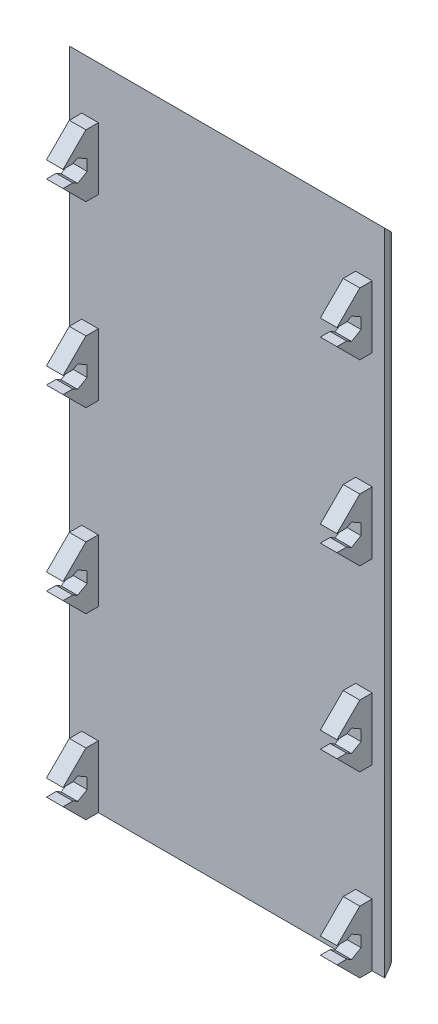
SolidWorks part; units mm, degrees
ref_plane "Front Plane" through (0, 0, 0) normal (0, 0, 1) x (1, 0, 0)
ref_plane "Top Plane" through (0, 0, 0) normal (0, 1, 0) x (1, 0, 0)
ref_plane "Right Plane" through (0, 0, 0) normal (1, 0, 0) x (0, 0, -1)
sketch "Sketch1" plane through (0, 0, 0) normal (0, 1, 0) x (1, 0, 0)
  line L0 (-9.2151, 0) -> (-9.2151, -10)
  line L1 (-9.2151, -10) -> (-5.2151, -10)
  line L2 (-5.2151, -10) -> (-5.2151, 0)
  line L3 (-5.2151, 0) -> (56.7849, 0)
  line L4 (56.7849, 0) -> (56.7849, -10)
  line L5 (56.7849, -10) -> (60.7849, -10)
  line L6 (60.7849, -10) -> (60.7849, 0)
  line L7 (60.7849, 0) -> (63.7849, 0)
  line L8 (-9.2151, 0) -> (-12.2151, 0)
  line L9 (-12.2151, 0) -> (-8.1737, 7)
  line L10 (-8.1737, 7) -> (59.7434, 7)
  line L11 (59.7434, 7) -> (63.7849, 0)
  line L12 (25.7849, 7) -> (25.7849, 0) construction
  dimension "D1" = 3
  dimension "D2" = 10
  dimension "D3" = 70
  dimension "D4" = 7
  dimension "D5" = 4
  dimension "D6" = 60
extrude "Boss-Extrude1" add sketch "Sketch1" along normal blind 156.5
sketch "Sketch4" plane through (60.7849, 0, 0) normal (1, 0, 0) x (0, 0, -1)
  line L0 (0, 156.5) -> (0, 0) construction
  line L1 (-37.5185, 156.5) -> (0, 156.5)
  line L2 (-37.5185, 156.5) -> (-37.5185, 144)
  line L3 (-37.5185, 144) -> (0, 144)
  line L4 (0, 156.5) -> (0, 144)
  line L5 (-37.5185, 156.5) -> (0, 144) construction
  line L6 (-37.5185, 144) -> (0, 156.5) construction
  line L7 (-10, 156.5) -> (0, 156.5) construction
  point P0 (-18.7592, 150.25)
  dimension "D1" = 12.5
extrude "Cut-Extrude1" cut sketch "Sketch4" against normal through all
sketch "Sketch5" plane through (60.7849, 0, 0) normal (1, 0, 0) x (0, 0, -1)
  line L0 (0, 156.5) -> (0, 0) construction
  line L1 (-33.3149, 129) -> (0, 129)
  line L2 (-33.3149, 129) -> (-33.3149, 101)
  line L3 (-33.3149, 101) -> (0, 101)
  line L4 (0, 129) -> (0, 101)
  line L5 (-33.3149, 129) -> (0, 101) construction
  line L6 (-33.3149, 101) -> (0, 129) construction
  line L7 (-10, 144) -> (0, 144) construction
  point P0 (-16.6574, 115)
  dimension "D1" = 28
  dimension "D2" = 15
extrude "Cut-Extrude2" cut sketch "Sketch5" against normal through all
sketch "Sketch6" plane through (0, 0, 0) normal (1, 0, 0) x (0, 0, -1)
  line L0 (-10, 144) -> (-10, 129) construction
  line L1 (-2.7, 137.8279) -> (-5, 139.1558)
  line L2 (-5, 139.1558) -> (-7.3, 137.8279)
  line L3 (-7.3, 137.8279) -> (-7.3, 135.1721)
  line L4 (-7.3, 135.1721) -> (-5, 133.8442)
  line L5 (-5, 133.8442) -> (-2.7, 135.1721)
  line L6 (-2.7, 135.1721) -> (-2.7, 137.8279)
  line L7 (-10, 144) -> (0, 144) construction
  line L8 (-6.15, 138.4919) -> (-10, 138.4919)
  line L9 (-6.15, 134.5081) -> (-10, 134.5081)
  line L10 (-10, 134.5081) -> (-10, 138.4919)
  circle A1 centre (-5, 136.5) radius 2.3 construction
  dimension "D1" = 4.6
  dimension "D2" = 7.5
  dimension "D3" = 5
extrude "Cut-Extrude3" cut sketch "Sketch6" against normal through all and the other way through all contours L10 L9 L4 L3 L2 L8 | L5 L6 L1 L2 L3 L4 region at (0, 136.5, 5) region at (0, 136.5, 8.5351)
pattern_linear "LPattern1" count 4 spacing 43 along (0, -1, 0) of "Cut-Extrude2", "Cut-Extrude3"
chamfer "Chamfer3" distance 7 angle 45 1 edges at (25.7849, 156.5, -7)
fillet "Fillet1" radius 8 2 edges at (-8.1737, 74.75, -7) (59.7434, 74.75, -7)
chamfer "Chamfer5" distance 7 angle 45 16 edges at (58.7849, 43, 10) (58.7849, 144, 10) (58.7849, 129, 10) (-7.2151, 144, 10) (-7.2151, 129, 10) (-7.2151, 101, 10) (-7.2151, 86, 10) (58.7849, 101, 10) (58.7849, 86, 10) (58.7849, 58, 10) (58.7849, 0, 10) (58.7849, 15, 10) (-7.2151, 0, 10) (-7.2151, 15, 10) (-7.2151, 58, 10) (-7.2151, 43, 10)
sketch "Sketch7" plane through (0, 0, -7) normal (0, 0, -1) x (-1, 0, 0)
  line L8 (3.5549, 82.737) -> (-11.316, 82.737) construction
  line L14 (-11.316, 128.6101) -> (-40.2538, 128.6101) construction
  line L20 (-11.316, 128.6101) -> (-11.316, 82.737) construction
  line L22 (-40.2538, 128.6101) -> (-40.2538, 82.737) construction
  line L23 (-11.316, 82.737) -> (-40.2538, 82.737) construction
  line L24 (3.5549, 0) -> (3.5549, 149.5) construction
  line L25 (-11.316, 127.6101) -> (-11.316, 116.1874)
  line L26 (-12.316, 128.6101) -> (-39.2538, 128.6101)
  line L27 (-11.316, 115.6101) -> (-40.2538, 115.6101) construction
  line L28 (-40.2538, 127.6101) -> (-40.2538, 115.6101)
  line L29 (-40.2538, 82.737) -> (-55.1246, 82.737) construction
  line L30 (-55.1246, 149.5) -> (-55.1246, 0) construction
  line L31 (-11.316, 149.5) -> (-11.316, 128.6101) construction
  line L32 (3.5549, 149.5) -> (-55.1246, 149.5) construction
  line L35 (-11.316, 107.5272) -> (-17.816, 103.7744)
  line L38 (-25.316, 99.4443) -> (-39.7538, 91.1086)
  line L39 (-11.316, 107.5272) -> (-11.316, 93.237)
  line L40 (-40.2538, 90.2426) -> (-40.2538, 82.737)
  line L41 (-40.2538, 82.737) -> (-32.316, 87.3199)
  line L42 (-32.316, 87.3199) -> (-32.316, 93.237) construction
  line L43 (-18.316, 102.9084) -> (-18.316, 93.237)
  line L44 (-11.316, 93.237) -> (-32.316, 93.237) construction
  line L45 (-25.316, 99.4443) -> (-25.316, 93.237)
  line L46 (-18.316, 93.237) -> (-25.316, 93.237) construction
  line L47 (-39.7538, 107.2744) -> (-18.566, 119.5072)
  line L48 (-40.2538, 115.6101) -> (-40.2538, 106.9857) construction
  line L49 (-11.316, 82.737) -> (-40.2538, 82.737) construction
  line L50 (-40.2538, 106.4084) -> (-40.2538, 100.5631)
  line L51 (-32.316, 87.3199) -> (-30.9714, 88.0962)
  line L52 (-11.816, 115.3214) -> (-31.566, 103.9187)
  line L53 (-33.2538, 121.1101) -> (-33.2538, 119.3988)
  line L54 (-31.566, 103.0527) -> (-25.316, 99.4443)
  line L55 (-32.316, 95.4028) -> (-39.7538, 99.6971)
  line L56 (-33.5038, 118.9657) -> (-40.2538, 115.0686)
  line L57 (-40.2538, 115.0686) -> (-40.2538, 115.6101)
  line L58 (-32.7538, 121.6101) -> (-18.816, 121.6101)
  line L59 (-18.316, 121.1101) -> (-18.316, 119.9402)
  line L60 (-11.316, 121.6101) -> (-18.316, 121.6101) construction
  line L61 (-33.2538, 121.6101) -> (-40.2538, 121.6101) construction
  line L62 (-40.2538, 128.6101) -> (-11.316, 128.6101) construction
  line L63 (-11.316, 128.6101) -> (-11.316, 82.737) construction
  arc A7 (-11.316, 93.237) -> (-32.316, 93.237) centre (-21.816, 93.237) cw
  arc A8 (-18.316, 93.237) -> (-25.316, 93.237) centre (-21.816, 93.237) cw
  arc A9 (-17.816, 103.7744) -> (-18.316, 102.9084) centre (-17.316, 102.9084) ccw
  arc A10 (-11.816, 115.3214) -> (-11.316, 116.1874) centre (-12.316, 116.1874) ccw
  arc A11 (-11.316, 127.6101) -> (-12.316, 128.6101) centre (-12.316, 127.6101) ccw
  arc A12 (-39.7538, 91.1086) -> (-40.2538, 90.2426) centre (-39.2538, 90.2426) ccw
  arc A13 (-39.2538, 128.6101) -> (-40.2538, 127.6101) centre (-39.2538, 127.6101) ccw
  arc A14 (-40.2538, 106.4084) -> (-39.7538, 107.2744) centre (-39.2538, 106.4084) cw
  arc A15 (-39.7538, 99.6971) -> (-40.2538, 100.5631) centre (-39.2538, 100.5631) cw
  arc A16 (-32.7538, 121.6101) -> (-33.2538, 121.1101) centre (-32.7538, 121.1101) ccw
  arc A17 (-33.5038, 118.9657) -> (-33.2538, 119.3988) centre (-33.7538, 119.3988) ccw
  arc A18 (-18.316, 121.1101) -> (-18.816, 121.6101) centre (-18.816, 121.1101) ccw
  arc A19 (-18.566, 119.5072) -> (-18.316, 119.9402) centre (-18.816, 119.9402) ccw
  arc A20 (-31.566, 103.0527) -> (-31.566, 103.9187) centre (-31.316, 103.4857) cw
  point P59 (-40.2538, 106.9857)
  point P63 (-40.2538, 99.9857)
  dimension "D11" = 7
  dimension "D12" = 30
  dimension "D10" = 7
  dimension "D14" = 0.5
  dimension "D16" = 7
  dimension "D6" = 7
  dimension "D13" = 1
  dimension "D2" = 1
  dimension "0.5" = 1
  dimension "D18" = 1
  dimension "D4" = 0.5
  dimension "D1" = 7
  dimension "D3" = 7
  dimension "D5" = 7
  dimension "D7" = 7
  dimension "D8" = 7
  dimension "D9" = 7
  dimension "D15" = 30
  dimension "D17" = 7
extrude "Cut-Extrude4" cut sketch "Sketch7" against normal blind 1 contours L54 A20 L52 A10 L25 A11 L26 A13 L28 L57 L56 L53 L58 L59 L47 A14 L50 A15 L55 L38 | L38 A12 L40 L41 L51 A7 L39 L35 A9 L43 A8 L45 region at (11.7564, 121.8988, -7) region at (25.697, 96.3406, -7)
sketch "Sketch8" plane through (0, 0, -7) normal (0, 0, -1) x (-1, 0, 0)
  line L0 (-40.2538, 128.6101) -> (-40.2538, 43.6101) construction
  line L1 (-55.1246, 149.5) -> (-55.1246, 0) construction
  line L2 (-25.7849, 128.6101) -> (-55.1246, 128.6101) construction
  line L3 (-12.316, 128.6101) -> (-39.2538, 128.6101) construction
  line L5 (-40.2538, 127.6101) -> (-40.2538, 115.0686) construction
  text T0 "DREAm" font "VALORANT" height in points 24
  dimension "D1" = 85
extrude "Cut-Extrude5" cut sketch "Sketch8" against normal blind 1
fillet "Fillet2" radius 0.5 2 edges at (32.316, 95.4028, -6.5) (25.316, 99.4443, -6.5)
sketch "Sketch9" plane through (0, 0, -7) normal (0, 0, -1) x (-1, 0, 0)
  line L0 (-13.816, 71.5072) -> (-25.316, 71.5072)
  line L1 (-25.316, 71.5072) -> (-25.316, 69.0072)
  line L2 (-25.316, 69.0072) -> (-13.816, 69.0072)
  line L3 (-13.816, 69.0072) -> (-13.816, 64.7572)
  line L4 (-13.816, 64.7572) -> (-11.316, 64.7572)
  line L5 (-11.316, 64.7572) -> (-11.316, 75.7572)
  line L6 (-11.316, 75.7572) -> (-13.816, 75.7572)
  line L7 (-13.816, 75.7572) -> (-13.816, 71.5072)
  line L8 (-11.316, 62.2572) -> (-11.316, 59.7572)
  line L9 (-11.316, 59.7572) -> (-25.316, 59.7572)
  line L10 (-25.316, 59.7572) -> (-25.316, 62.2572)
  line L11 (-25.316, 62.2572) -> (-11.316, 62.2572)
  line L12 (-11.316, 75.7572) -> (-11.316, 12.6828) construction
  line L13 (-25.316, 71.5072) -> (-25.316, 10.6582) construction
  line L14 (-11.316, 57.2572) -> (-25.316, 57.2572)
  line L15 (-25.316, 57.2572) -> (-25.316, 54.7572)
  line L16 (-25.316, 54.7572) -> (-16.316, 54.7572)
  line L17 (-16.316, 54.7572) -> (-25.316, 49.5611)
  line L18 (-25.316, 49.5611) -> (-25.316, 47.0611)
  line L19 (-25.316, 47.0611) -> (-16.316, 47.0611)
  line L20 (-16.316, 47.0611) -> (-25.316, 41.8649)
  line L21 (-25.316, 41.8649) -> (-25.316, 41.4782)
  line L22 (-25.316, 41.4782) -> (-20.9858, 41.4782)
  line L23 (-20.9858, 41.4782) -> (-11.316, 47.0611)
  line L24 (-11.316, 47.0611) -> (-11.316, 49.5611)
  line L25 (-11.316, 49.5611) -> (-20.316, 49.5611)
  line L26 (-20.316, 49.5611) -> (-11.316, 54.7572)
  line L27 (-11.316, 54.7572) -> (-11.316, 57.2572)
  line L28 (-11.316, 47.0611) -> (-25.316, 38.9782) construction
  line L29 (-25.316, 38.9782) -> (-11.316, 38.9782)
  line L30 (-11.316, 38.9782) -> (-11.316, 36.4782)
  line L31 (-11.316, 36.4782) -> (-25.316, 28.3953)
  line L32 (-25.316, 28.3953) -> (-25.316, 31.282)
  line L33 (-25.316, 31.282) -> (-23.066, 32.5811)
  line L34 (-23.066, 32.5811) -> (-25.316, 36.4782)
  line L35 (-25.316, 36.4782) -> (-25.316, 38.9782)
  line L36 (-16.316, 36.4782) -> (-20.9009, 33.8311)
  line L38 (-22.4292, 36.4782) -> (-16.316, 36.4782)
  line L39 (-22.4292, 36.4782) -> (-20.9009, 33.8311)
  line L40 (-11.316, 30.8953) -> (-15.9858, 30.8953)
  line L41 (-15.9858, 30.8953) -> (-20.316, 28.3953)
  line L42 (-20.316, 28.3953) -> (-16.316, 28.3953)
  line L43 (-16.316, 28.3953) -> (-25.316, 23.1991)
  line L44 (-25.316, 23.1991) -> (-25.316, 20.6991)
  line L45 (-25.316, 20.6991) -> (-11.316, 20.6991)
  line L46 (-11.316, 20.6991) -> (-11.316, 23.1991)
  line L47 (-11.316, 23.1991) -> (-20.316, 23.1991)
  line L48 (-20.316, 23.1991) -> (-11.316, 28.3953)
  line L49 (-11.316, 28.3953) -> (-11.316, 30.8953)
  line L50 (-11.316, 18.1991) -> (-11.316, 15.6991)
  line L51 (-11.316, 15.6991) -> (-17.316, 15.6991)
  line L52 (-17.316, 15.6991) -> (-17.316, 9.6991)
  line L53 (-17.316, 9.6991) -> (-11.316, 9.6991)
  line L54 (-11.316, 9.6991) -> (-11.316, 7.1991)
  line L55 (-11.316, 7.1991) -> (-25.316, 7.1991)
  line L56 (-25.316, 7.1991) -> (-25.316, 9.6991)
  line L57 (-25.316, 9.6991) -> (-19.816, 9.6991)
  line L58 (-19.816, 9.6991) -> (-19.816, 15.6991)
  line L59 (-19.816, 15.6991) -> (-25.316, 15.6991)
  line L60 (-25.316, 15.6991) -> (-25.316, 18.1991)
  line L61 (-25.316, 18.1991) -> (-11.316, 18.1991)
  line L62 (-11.316, 107.5272) -> (-11.316, 93.237) construction
  dimension "D1" = 2.5
  dimension "D2" = 14
  dimension "D3" = 11
  dimension "D4" = 2.5
  dimension "D5" = 2.5
  dimension "D6" = 2.5
  dimension "D7" = 30
  dimension "D8" = 2.5
  dimension "D9" = 2.5
  dimension "D10" = 60
  dimension "D11" = 2.5
  dimension "D12" = 2.5
  dimension "D13" = 30
  dimension "D14" = 60
  dimension "D15" = 2.5
  dimension "D16" = 2.5
  dimension "D17" = 2.5
  dimension "D18" = 2.5
  dimension "D19" = 2.5
  dimension "D20" = 2.5
  dimension "D21" = 2.5
  dimension "D22" = 30
  dimension "D23" = 2.5
  dimension "D24" = 11
  dimension "D25" = 6
  dimension "D26" = 2.5
extrude "Cut-Extrude6" cut sketch "Sketch9" against normal blind 1
